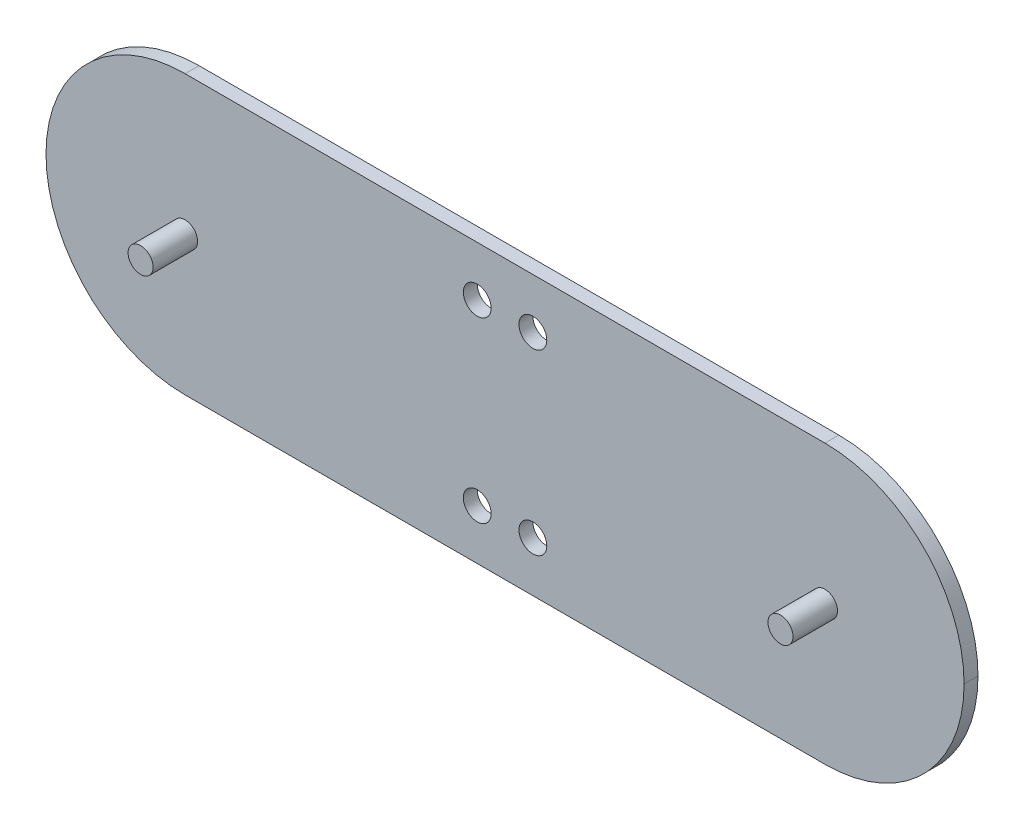
SolidWorks part; units mm, degrees
ref_plane "Front Plane" through (0, 0, 0) normal (0, 0, 1) x (1, 0, 0)
ref_plane "Top Plane" through (0, 0, 0) normal (0, 1, 0) x (1, 0, 0)
ref_plane "Right Plane" through (0, 0, 0) normal (1, 0, 0) x (0, 0, -1)
sketch "Sketch1" plane through (0, 0, 0) normal (0, 0, 1) x (1, 0, 0)
  line L1 (82.5, 25) -> (-82.5, 25)
  line L2 (82.5, 25) -> (82.5, -25)
  line L3 (82.5, -25) -> (-82.5, -25)
  line L4 (-82.5, 25) -> (-82.5, -25)
  line L5 (82.5, 25) -> (-82.5, -25) construction
  line L6 (82.5, -25) -> (-82.5, 25) construction
  point P0 (0, 0)
  dimension "D1" = 50
  dimension "D2" = 165
extrude "Boss-Extrude1" add sketch "Sketch1" along normal blind 2.5
fillet "Fillet1" radius 25 4 edges at (-82.5, -25, 1.25) (-82.5, 25, 1.25) (82.5, -25, 1.25) (82.5, 25, 1.25)
sketch "Sketch2" plane through (0, 0, 2.5) normal (0, 0, 1) x (1, 0, 0)
  line L0 (0, 0) -> (0, 16)
  line L1 (0, 16) -> (-5, 16)
  line L2 (-5, 16) -> (5, 16)
  circle A0 centre (-5, 16) radius 2.5
  circle A1 centre (5, 16) radius 2.5
  dimension "D4" = 5
  dimension "D5" = 5
  dimension "D1" = 16
  dimension "D2" = 5
  dimension "D3" = 10
extrude "Cut-Extrude1" cut sketch "Sketch2" against normal blind 2.5 contours A0 | A1 region at (-7.4293, 16, 2.5) region at (5, 18.4293, 2.5)
mirror "Mirror1" about plane through (0, 0, 0) normal (0, 1, 0) of "Cut-Extrude1"
sketch "Sketch4" plane through (0, 0, 2.5) normal (0, 0, 1) x (1, 0, 0)
  line L0 (0, 0) -> (-57.5, 0)
  circle A0 centre (-57.5, 0) radius 2.25
  dimension "D2" = 4.5
  dimension "D1" = 57.5
extrude "Boss-Extrude2" add sketch "Sketch4" along normal blind 8 contours A0 region at (-59.6864, 0, 2.5)
mirror "Mirror3" about plane through (0, 0, 0) normal (1, 0, 0) of "Boss-Extrude2"
